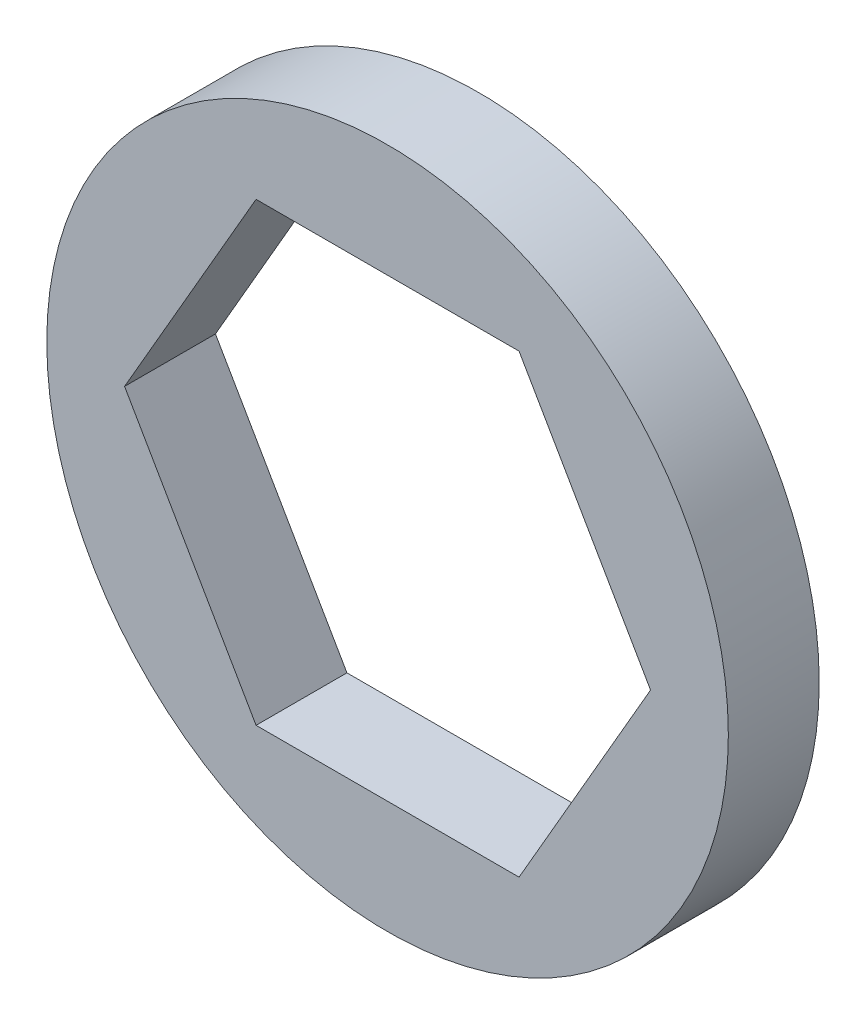
SolidWorks part; units mm, degrees
ref_plane "Front Plane" through (0, 0, 0) normal (0, 0, 1) x (1, 0, 0)
ref_plane "Top Plane" through (0, 0, 0) normal (0, 1, 0) x (1, 0, 0)
ref_plane "Right Plane" through (0, 0, 0) normal (1, 0, 0) x (0, 0, -1)
sketch "Sketch1" plane through (0, 0, 0) normal (0, 0, 1) x (1, 0, 0)
  line L1 (5.7879, 0) -> (2.894, 5.0125)
  line L2 (2.894, 5.0125) -> (-2.894, 5.0125)
  line L3 (-2.894, 5.0125) -> (-5.7879, 0)
  line L4 (-5.7879, 0) -> (-2.894, -5.0125)
  line L5 (-2.894, -5.0125) -> (2.894, -5.0125)
  line L6 (2.894, -5.0125) -> (5.7879, 0)
  circle A0 centre (0, 0) radius 7.5
  circle A1 centre (0, 0) radius 5.0125 construction
  dimension "D1" = 10.025
  dimension "D2" = 15
extrude "Boss-Extrude1" add sketch "Sketch1" along normal mid plane 2
ref_axis "Axis1" through (0, 0, -13.3344) along (0, 0, 1)
